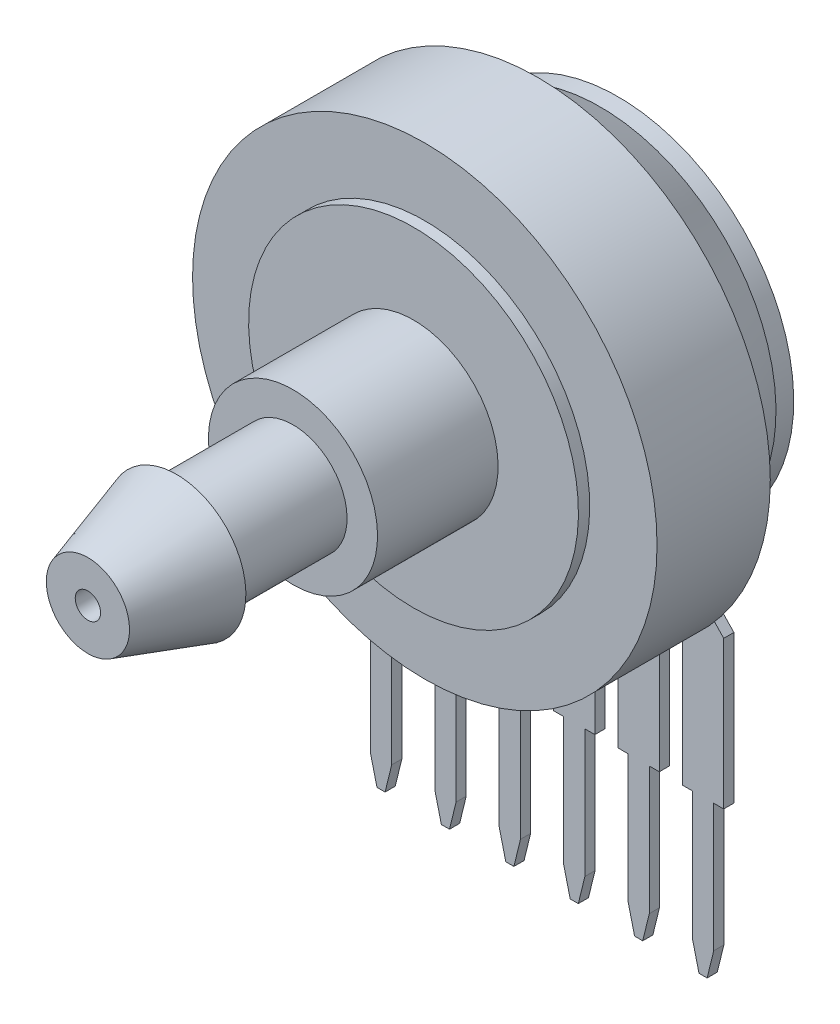
SolidWorks part; units mm, degrees
ref_plane "Front Plane" through (0, 0, 0) normal (0, 0, 1) x (1, 0, 0)
ref_plane "Top Plane" through (0, 0, 0) normal (0, 1, 0) x (1, 0, 0)
ref_plane "Right Plane" through (0, 0, 0) normal (1, 0, 0) x (0, 0, -1)
sketch "Sketch1" plane through (0, 0, 0) normal (0, 0, 1) x (1, 0, 0)
  line L0 (-7.165, -6.4913) -> (-7.165, -7.1728)
  line L1 (-4.625, -8.5934) -> (-4.625, -12.32)
  line L2 (-2.995, -12.32) -> (-2.995, -8.5831)
  line L3 (-7.165, -8.5934) -> (-7.165, -12.32)
  line L4 (-7.165, -12.32) -> (-6.77, -12.32)
  line L5 (-6.77, -12.32) -> (-6.77, -17.3607)
  line L6 (-6.77, -17.3607) -> (-6.5103, -18.42)
  line L7 (-6.5103, -18.42) -> (-6.1897, -18.42)
  line L8 (-6.1897, -18.42) -> (-5.93, -17.3607)
  line L9 (-5.93, -17.3607) -> (-5.93, -12.32)
  line L10 (-5.93, -12.32) -> (-5.535, -12.32)
  line L11 (-5.535, -12.32) -> (-5.535, -8.5831)
  line L12 (-3.39, -12.32) -> (-2.995, -12.32)
  line L13 (-3.39, -17.3607) -> (-3.39, -12.32)
  line L14 (-4.23, -12.32) -> (-4.23, -17.3607)
  line L15 (-4.625, -12.32) -> (-4.23, -12.32)
  line L16 (-3.6497, -18.42) -> (-3.39, -17.3607)
  line L17 (-4.23, -17.3607) -> (-3.9703, -18.42)
  line L18 (-3.9703, -18.42) -> (-3.6497, -18.42)
  line L19 (-2.085, -8.5934) -> (-2.085, -12.32)
  line L20 (-0.455, -12.32) -> (-0.455, -8.5831)
  line L21 (-0.85, -12.32) -> (-0.455, -12.32)
  line L22 (-0.85, -17.3607) -> (-0.85, -12.32)
  line L23 (-1.69, -12.32) -> (-1.69, -17.3607)
  line L24 (-2.085, -12.32) -> (-1.69, -12.32)
  line L25 (-1.1097, -18.42) -> (-0.85, -17.3607)
  line L26 (-1.69, -17.3607) -> (-1.4303, -18.42)
  line L27 (-1.4303, -18.42) -> (-1.1097, -18.42)
  line L28 (0.455, -8.5934) -> (0.455, -12.32)
  line L29 (2.085, -12.32) -> (2.085, -8.5831)
  line L30 (1.69, -12.32) -> (2.085, -12.32)
  line L31 (1.69, -17.3607) -> (1.69, -12.32)
  line L32 (0.85, -12.32) -> (0.85, -17.3607)
  line L33 (0.455, -12.32) -> (0.85, -12.32)
  line L34 (1.4303, -18.42) -> (1.69, -17.3607)
  line L35 (0.85, -17.3607) -> (1.1097, -18.42)
  line L36 (1.1097, -18.42) -> (1.4303, -18.42)
  line L37 (2.995, -8.5934) -> (2.995, -12.32)
  line L38 (4.625, -12.32) -> (4.625, -8.5831)
  line L39 (4.23, -12.32) -> (4.625, -12.32)
  line L40 (4.23, -17.3607) -> (4.23, -12.32)
  line L41 (3.39, -12.32) -> (3.39, -17.3607)
  line L42 (2.995, -12.32) -> (3.39, -12.32)
  line L43 (3.9703, -18.42) -> (4.23, -17.3607)
  line L44 (3.39, -17.3607) -> (3.6497, -18.42)
  line L45 (3.6497, -18.42) -> (3.9703, -18.42)
  line L46 (5.535, -8.5934) -> (5.535, -12.32)
  line L47 (7.165, -12.32) -> (7.165, -8.5831)
  line L48 (6.77, -12.32) -> (7.165, -12.32)
  line L49 (6.77, -17.3607) -> (6.77, -12.32)
  line L50 (5.93, -12.32) -> (5.93, -17.3607)
  line L51 (5.535, -12.32) -> (5.93, -12.32)
  line L52 (6.5103, -18.42) -> (6.77, -17.3607)
  line L53 (5.93, -17.3607) -> (6.1897, -18.42)
  line L54 (6.1897, -18.42) -> (6.5103, -18.42)
  line L55 (-7.165, -8.5934) -> (-4.625, -8.5934) construction
  line L56 (-6.35, -18.42) -> (-6.35, -17.3607) construction
  line L57 (-6.35, -17.3607) -> (-6.77, -17.3607) construction
  line L58 (-5.93, -17.3607) -> (-6.35, -17.3607) construction
  line L59 (0.455, -12.32) -> (0, -12.32) construction
  line L60 (0, -12.32) -> (-0.455, -12.32) construction
  line L62 (0, 0) -> (-11.555, 0) construction
  line L64 (0, 0) -> (0, 0.5736) construction
  line L67 (-7.165, -6.4913) -> (-5.0517, -4.2591)
  line L68 (-5.535, -8.5831) -> (-5.535, -6.9232)
  line L69 (-5.535, -6.9232) -> (-3.8372, -5.1299)
  line L70 (-7.165, -6.4913) -> (-5.535, -6.9232) construction
  line L71 (-6.35, -6.7073) -> (0, 0) construction
  line L72 (0, 0) -> (0, -8.5831) construction
  line L73 (5.535, -6.9232) -> (3.8372, -5.1299)
  line L74 (5.535, -8.5831) -> (5.535, -6.9232)
  line L75 (7.165, -6.4913) -> (5.0517, -4.2591)
  arc A0 (-7.165, -7.1728) -> (-7.165, -8.5934) centre (-7.165, -7.8831) cw
  circle A1 centre (0, 0) radius 0.8115
  circle A2 centre (0, 0) radius 5.401
  circle A7 centre (0, 0) radius 6.8776
  circle A8 centre (0, 0) radius 7.9339
  dimension "D1" = 2.54
  dimension "D2" = 1.63
  dimension "D3" = 0.84
  dimension "D4" = 6.1
  dimension "D5" = 18.42
sketch "Sketch2" plane through (0, 0, 0) normal (1, 0, 0) x (0, 0, -1)
  line L0 (0, -17.9671) -> (-0.2, -17.9671)
  line L3 (-0.2, -17.9671) -> (-0.2, -8.0916)
  line L4 (-0.2, -8.0916) -> (-2.2009, -6.93)
  line L9 (-2.2009, -6.93) -> (-2.795, -6.93)
  line L10 (-2.795, -6.93) -> (-2.795, 6.93)
  line L11 (-2.795, 6.93) -> (-2.0963, 6.93)
  line L14 (-2.0963, 6.93) -> (-0.3582, 7.9084)
  line L15 (-0.3582, 7.9084) -> (0, 7.9084)
  line L18 (0, 7.9084) -> (0, -17.9671)
  line L19 (0, 7.9084) -> (0, 9.9029) construction
  line L20 (2.795, -6.93) -> (2.795, 6.93)
  line L21 (-0.3582, -9.1593) -> (-4.8238, -9.1593)
  line L26 (0.2, -17.9671) -> (0.2, -8.0916)
  line L27 (-4.8238, -9.1593) -> (-4.8238, -6.5038)
  line L28 (-4.8238, -6.5038) -> (-5.2679, -6.5038)
  line L29 (-5.2679, -6.5038) -> (-5.2679, -3.3343)
  line L30 (-5.2679, -3.3343) -> (-10.0223, -3.3343)
  line L31 (-10.0223, -3.3343) -> (-10.0223, -2.1321)
  line L32 (-10.0223, -2.1321) -> (-14.6126, -2.1321)
  line L33 (-14.6126, -2.1321) -> (-14.6126, -2.7332)
  line L34 (-14.6126, -2.7332) -> (-18.1101, -1.6402)
  line L35 (-18.1101, -1.6402) -> (-18.1101, 0)
  line L36 (-18.1101, 0) -> (-4.175, 0)
  line L37 (-0.3582, 7.9084) -> (-0.3582, 9.1593)
  line L38 (-0.3582, 9.1593) -> (-4.8238, 9.1593)
  line L39 (0, 0) -> (-1.7159, 0) construction
  line L40 (-4.8238, 9.1593) -> (-4.8238, 6.5038)
  line L41 (-14.6126, 2.7332) -> (-18.1101, 1.6402)
  line L42 (-14.6126, 2.1321) -> (-14.6126, 2.7332)
  line L43 (-10.0223, 2.1321) -> (-14.6126, 2.1321)
  line L44 (-10.0223, 3.3343) -> (-10.0223, 2.1321)
  line L45 (-5.2679, 3.3343) -> (-10.0223, 3.3343)
  line L46 (-5.2679, 6.5038) -> (-5.2679, 3.3343)
  line L47 (-4.8238, 6.5038) -> (-5.2679, 6.5038)
  point P10 (-2.795, 0)
  dimension "D1" = 16
  dimension "D2" = 13.86
  dimension "D3" = 5.59
  dimension "D4" = 0.4
sketch "Sketch7" plane through (0, 0, 0) normal (0, 0, 1) x (1, 0, 0)
  line L1 (-5.93, -12.32) -> (-5.535, -12.32) construction
  line L2 (-5.93, -17.3607) -> (-5.93, -12.32) construction
  line L3 (-6.1897, -18.42) -> (-5.93, -17.3607) construction
  line L4 (-6.5103, -18.42) -> (-6.1897, -18.42) construction
  line L5 (-6.77, -17.3607) -> (-6.5103, -18.42) construction
  line L6 (-6.77, -12.32) -> (-6.77, -17.3607) construction
  line L7 (-7.165, -12.32) -> (-6.77, -12.32) construction
  line L8 (-7.165, -8.5934) -> (-7.165, -12.32) construction
  line L10 (-4.625, -8.5934) -> (-4.625, -12.32) construction
  line L11 (-4.625, -12.32) -> (-4.23, -12.32) construction
  line L12 (-4.23, -12.32) -> (-4.23, -17.3607) construction
  line L13 (-4.23, -17.3607) -> (-3.9703, -18.42) construction
  line L14 (-3.9703, -18.42) -> (-3.6497, -18.42) construction
  line L15 (-3.6497, -18.42) -> (-3.39, -17.3607) construction
  line L16 (-3.39, -17.3607) -> (-3.39, -12.32) construction
  line L17 (-3.39, -12.32) -> (-2.995, -12.32) construction
  line L18 (-2.995, -12.32) -> (-2.995, -8.5831) construction
  line L19 (-0.455, -12.32) -> (-0.455, -8.5831) construction
  line L20 (-0.85, -12.32) -> (-0.455, -12.32) construction
  line L21 (-0.85, -17.3607) -> (-0.85, -12.32) construction
  line L22 (-1.1097, -18.42) -> (-0.85, -17.3607) construction
  line L23 (-1.4303, -18.42) -> (-1.1097, -18.42) construction
  line L24 (-1.69, -17.3607) -> (-1.4303, -18.42) construction
  line L25 (-1.69, -12.32) -> (-1.69, -17.3607) construction
  line L26 (-2.085, -12.32) -> (-1.69, -12.32) construction
  line L27 (-2.085, -8.5934) -> (-2.085, -12.32) construction
  line L28 (4.625, -12.32) -> (4.625, -8.5831) construction
  line L29 (4.23, -12.32) -> (4.625, -12.32) construction
  line L30 (4.23, -17.3607) -> (4.23, -12.32) construction
  line L31 (3.9703, -18.42) -> (4.23, -17.3607) construction
  line L32 (3.6497, -18.42) -> (3.9703, -18.42) construction
  line L33 (3.39, -17.3607) -> (3.6497, -18.42) construction
  line L34 (3.39, -12.32) -> (3.39, -17.3607) construction
  line L35 (2.995, -12.32) -> (3.39, -12.32) construction
  line L36 (2.995, -8.5934) -> (2.995, -12.32) construction
  line L37 (0.455, -8.5934) -> (0.455, -12.32) construction
  line L38 (0.455, -12.32) -> (0.85, -12.32) construction
  line L39 (0.85, -12.32) -> (0.85, -17.3607) construction
  line L40 (0.85, -17.3607) -> (1.1097, -18.42) construction
  line L41 (1.1097, -18.42) -> (1.4303, -18.42) construction
  line L42 (1.4303, -18.42) -> (1.69, -17.3607) construction
  line L43 (1.69, -17.3607) -> (1.69, -12.32) construction
  line L44 (1.69, -12.32) -> (2.085, -12.32) construction
  line L45 (2.085, -12.32) -> (2.085, -8.5831) construction
  line L47 (5.535, -12.32) -> (5.93, -12.32) construction
  line L48 (5.93, -12.32) -> (5.93, -17.3607) construction
  line L49 (5.93, -17.3607) -> (6.1897, -18.42) construction
  line L50 (6.1897, -18.42) -> (6.5103, -18.42) construction
  line L51 (6.5103, -18.42) -> (6.77, -17.3607) construction
  line L52 (6.77, -17.3607) -> (6.77, -12.32) construction
  line L53 (6.77, -12.32) -> (7.165, -12.32) construction
  line L55 (-7.165, -6.4913) -> (-7.165, -7.1728) construction
  line L56 (-5.93, -12.32) -> (-5.535, -12.32)
  line L57 (-5.93, -17.3607) -> (-5.93, -12.32)
  line L58 (-6.1897, -18.42) -> (-5.93, -17.3607)
  line L59 (-6.5103, -18.42) -> (-6.1897, -18.42)
  line L60 (-6.77, -17.3607) -> (-6.5103, -18.42)
  line L61 (-6.77, -12.32) -> (-6.77, -17.3607)
  line L62 (-7.165, -12.32) -> (-6.77, -12.32)
  line L63 (-7.165, -8.5934) -> (-7.165, -12.32)
  line L64 (-7.165, -6.4913) -> (-5.0517, -4.2591) construction
  line L65 (-4.625, -6.4464) -> (-4.625, -12.32)
  line L66 (-4.625, -12.32) -> (-4.23, -12.32)
  line L67 (-4.23, -12.32) -> (-4.23, -17.3607)
  line L68 (-4.23, -17.3607) -> (-3.9703, -18.42)
  line L69 (-3.9703, -18.42) -> (-3.6497, -18.42)
  line L70 (-3.6497, -18.42) -> (-3.39, -17.3607)
  line L71 (-3.39, -17.3607) -> (-3.39, -12.32)
  line L72 (-3.39, -12.32) -> (-2.995, -12.32)
  line L73 (-2.995, -12.32) -> (-2.995, -7.3469)
  line L74 (-0.455, -12.32) -> (-0.455, -7.9208)
  line L75 (-0.85, -12.32) -> (-0.455, -12.32)
  line L76 (-0.85, -17.3607) -> (-0.85, -12.32)
  line L77 (-1.1097, -18.42) -> (-0.85, -17.3607)
  line L78 (-1.4303, -18.42) -> (-1.1097, -18.42)
  line L79 (-1.69, -17.3607) -> (-1.4303, -18.42)
  line L80 (-1.69, -12.32) -> (-1.69, -17.3607)
  line L81 (-2.085, -12.32) -> (-1.69, -12.32)
  line L82 (-2.085, -7.655) -> (-2.085, -12.32)
  line L83 (4.625, -12.32) -> (4.625, -6.4464)
  line L84 (4.23, -12.32) -> (4.625, -12.32)
  line L85 (4.23, -17.3607) -> (4.23, -12.32)
  line L86 (3.9703, -18.42) -> (4.23, -17.3607)
  line L87 (3.6497, -18.42) -> (3.9703, -18.42)
  line L88 (3.39, -17.3607) -> (3.6497, -18.42)
  line L89 (3.39, -12.32) -> (3.39, -17.3607)
  line L90 (2.995, -12.32) -> (3.39, -12.32)
  line L91 (2.995, -7.3469) -> (2.995, -12.32)
  line L92 (0.455, -7.9208) -> (0.455, -12.32)
  line L93 (0.455, -12.32) -> (0.85, -12.32)
  line L94 (0.85, -12.32) -> (0.85, -17.3607)
  line L95 (0.85, -17.3607) -> (1.1097, -18.42)
  line L96 (1.1097, -18.42) -> (1.4303, -18.42)
  line L97 (1.4303, -18.42) -> (1.69, -17.3607)
  line L98 (1.69, -17.3607) -> (1.69, -12.32)
  line L99 (1.69, -12.32) -> (2.085, -12.32)
  line L100 (2.085, -12.32) -> (2.085, -7.655)
  line L101 (-5.535, -8.5831) -> (-5.535, -6.9232) construction
  line L102 (5.535, -12.32) -> (5.93, -12.32)
  line L103 (5.93, -12.32) -> (5.93, -17.3607)
  line L104 (5.93, -17.3607) -> (6.1897, -18.42)
  line L105 (6.1897, -18.42) -> (6.5103, -18.42)
  line L106 (6.5103, -18.42) -> (6.77, -17.3607)
  line L107 (6.77, -17.3607) -> (6.77, -12.32)
  line L108 (6.77, -12.32) -> (7.165, -12.32)
  line L109 (-5.535, -6.9232) -> (-3.8372, -5.1299) construction
  line L110 (7.165, -6.4913) -> (5.0517, -4.2591) construction
  line L111 (5.535, -6.9232) -> (3.8372, -5.1299) construction
  line L112 (5.535, -8.5831) -> (5.535, -6.9232) construction
  line L113 (7.165, -12.32) -> (7.165, -8.5831) construction
  line L114 (-7.165, -6.4913) -> (-7.165, -7.1728)
  line L115 (-7.165, -6.4913) -> (-5.9684, -5.2274)
  line L116 (-5.535, -12.32) -> (-5.535, -6.9232)
  line L117 (-5.535, -6.9232) -> (-4.8932, -6.2453)
  line L118 (7.165, -6.4913) -> (5.9684, -5.2274)
  line L119 (5.535, -6.9232) -> (4.8932, -6.2453)
  line L120 (5.535, -12.32) -> (5.535, -6.9232)
  line L121 (7.165, -12.32) -> (7.165, -6.4913)
  arc A0 (-7.165, -8.5934) -> (-7.165, -7.1728) centre (-7.165, -7.8831) ccw construction
  arc A1 (-7.165, -8.5934) -> (-7.165, -7.1728) centre (-7.165, -7.8831) ccw
  circle A2 centre (0, 0) radius 7.9339 construction
  arc A3 (-5.9684, -5.2274) -> (-4.8932, -6.2453) centre (0, 0) ccw
  arc A4 (-2.085, -7.655) -> (-0.455, -7.9208) centre (0, 0) ccw
  arc A5 (0.455, -7.9208) -> (2.085, -7.655) centre (0, 0) ccw
  arc A6 (2.995, -7.3469) -> (4.625, -6.4464) centre (0, 0) ccw
  arc A7 (4.8932, -6.2453) -> (5.9684, -5.2274) centre (0, 0) ccw
  arc A8 (-4.625, -6.4464) -> (-2.995, -7.3469) centre (0, 0) ccw
extrude "Extrude6" add sketch "Sketch7" along normal up to vertex (0.2 mm away) and the other way up to vertex (0.2 mm away) up to point (0, -17.9671, 0.2) other way up to point (0, -17.9671, -0.2)
sketch "Sketch8" plane through (0, 0, 0) normal (1, 0, 0) x (0, 0, -1)
  line L0 (-14.6126, 2.7332) -> (-18.1101, 1.6402) construction
  line L1 (2.795, -6.93) -> (2.795, 6.93) construction
  line L2 (0, 7.9339) -> (0, -7.9339) construction
  line L3 (2.795, 0) -> (2.795, 6.93)
  line L4 (0, 7.9339) -> (0, -7.9339) construction
  line L5 (0.3582, 7.9084) -> (2.0963, 6.93)
  line L6 (2.795, 0) -> (8.385, 0) construction
  line L7 (2.0963, 6.93) -> (2.795, 6.93)
  line L8 (-18.1101, 0) -> (2.795, 0)
  line L9 (-14.6126, 2.1321) -> (-14.6126, 2.7332) construction
  line L10 (-10.0223, 2.1321) -> (-14.6126, 2.1321) construction
  line L11 (-10.0223, 3.3343) -> (-10.0223, 2.1321) construction
  line L12 (-5.2679, 3.3343) -> (-10.0223, 3.3343) construction
  line L13 (-0.2, -17.9671) -> (0, -17.9671)
  line L14 (-0.2, -8.0916) -> (-0.2, -17.9671)
  line L15 (-2.2009, -6.93) -> (-0.2, -8.0916)
  line L16 (-2.795, -6.93) -> (-2.2009, -6.93)
  line L17 (-2.795, 6.93) -> (-2.795, -6.93)
  line L18 (-2.0963, 6.93) -> (-2.795, 6.93)
  line L19 (-0.3582, 7.9084) -> (-2.0963, 6.93)
  line L20 (0, 7.9084) -> (-0.3582, 7.9084)
  line L21 (0, -17.9671) -> (0, 7.9084)
  line L22 (-5.2679, 6.5038) -> (-5.2679, 3.3343) construction
  line L23 (-4.8238, 6.5038) -> (-5.2679, 6.5038) construction
  line L24 (-4.8238, 9.1593) -> (-4.8238, 6.5038) construction
  line L25 (-0.3582, 9.1593) -> (-4.8238, 9.1593) construction
  line L26 (-18.1101, -1.6402) -> (-18.1101, 0) construction
  line L27 (-18.1101, 0) -> (-18.1101, 1.6402)
  line L29 (0.3582, 7.9084) -> (-0.3582, 7.9084)
  line L30 (-0.3582, 7.9084) -> (-0.3582, 9.1593) construction
  line L31 (-14.6126, 2.7332) -> (-18.1101, 1.6402)
  line L32 (-14.6126, 2.1321) -> (-14.6126, 2.7332)
  line L33 (-10.0223, 2.1321) -> (-14.6126, 2.1321)
  line L34 (-10.0223, 3.3343) -> (-10.0223, 2.1321)
  line L35 (-5.2679, 3.3343) -> (-10.0223, 3.3343)
  line L36 (-5.2679, 6.5038) -> (-5.2679, 3.3343)
  line L37 (-4.8238, 6.5038) -> (-5.2679, 6.5038)
  line L38 (-4.8238, 9.1593) -> (-4.8238, 6.5038)
  line L39 (-0.3582, 9.1593) -> (-4.8238, 9.1593)
  line L40 (-0.3582, 7.9084) -> (-0.3582, 9.1593)
  dimension "D1" = 0
revolve "Revolve1" add sketch "Sketch8" angle 360 about L6
hole_wizard "Ø1.0 (1) Diameter Hole1" positions "3DSketch1" profile "Sketch9" hole size "Ø1.0" standard "Ansi Metric"
sketch3d "3DSketch1"
  circle A0 centre (0, 0, 18.1101) radius 1.6402 construction
  point P0 (0, 0, 18.1101)
  point P6 (0, 0, 19.7503)
sketch "Sketch9" plane through (0, 0, 18.1101) normal (1, 0, 0) x (0, -1, 0)
  line L0 (0, 0) -> (0, 14.2704)
  line L1 (0, 14.2704) -> (0.5, 13.97)
  line L2 (0.5, 13.97) -> (0.5, 0)
  line L5 (0.5, 0) -> (0, 0)
  line L10 (0, 14.2704) -> (-0.5, 13.97) construction
  line L11 (0, -6.35) -> (0, 107.95) construction
  dimension "Hole Dia." = 1
  dimension "Hole Depth" = 13.97
  dimension "Drill Angle" = 118
